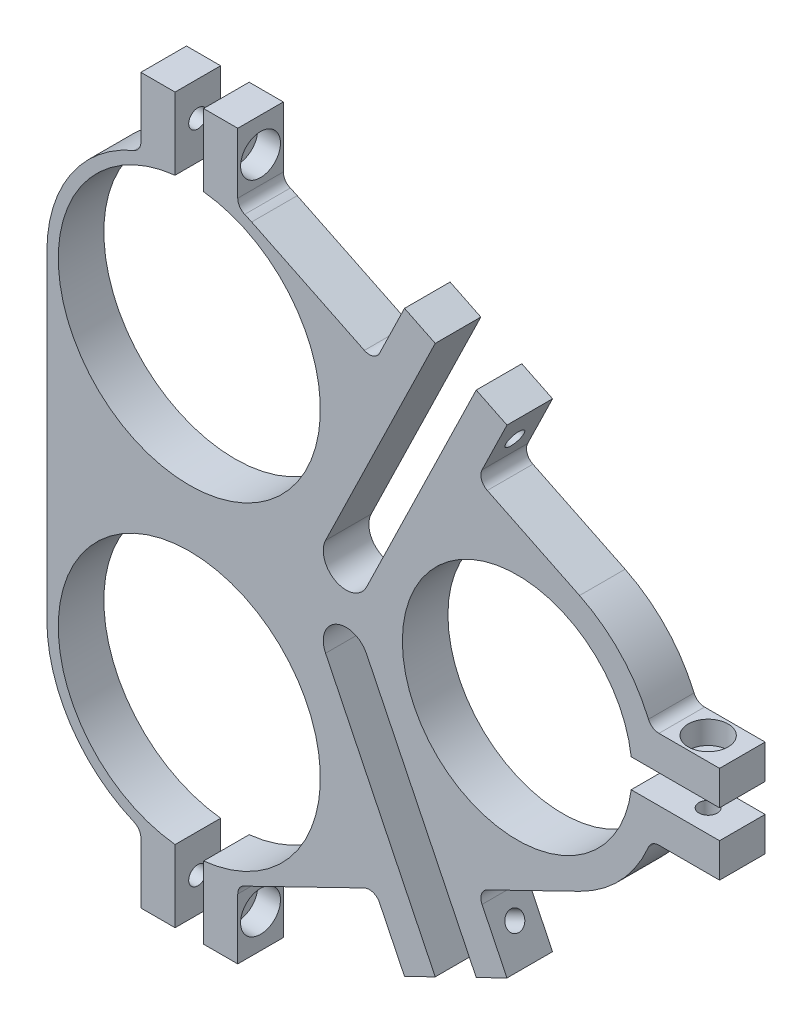
SolidWorks part; units mm, degrees
ref_plane "Front Plane" through (0, 0, 0) normal (0, 0, 1) x (1, 0, 0)
ref_plane "Top Plane" through (0, 0, 0) normal (0, 1, 0) x (1, 0, 0)
ref_plane "Right Plane" through (0, 0, 0) normal (1, 0, 0) x (0, 0, -1)
sketch "Sketch1" plane through (0, 0, 0) normal (0, 0, 1) x (1, 0, 0)
  line L0 (-39.6875, 88.9) -> (-39.6875, 0)
  line L1 (-39.6875, 44.45) -> (91.3606, 44.45) construction
  line L2 (17.3633, 124.5877) -> (51.6235, 107.919)
  line L3 (3.9688, -36.2962) -> (3.9688, -56.3731)
  line L4 (0, 88.9) -> (0, 0) construction
  line L5 (-13.4938, -37.3231) -> (-13.4938, -56.3731)
  line L6 (3.9688, -56.3731) -> (13.4938, -56.3731)
  line L7 (-3.9688, -56.3731) -> (-13.4938, -56.3731)
  line L8 (13.4938, -37.3231) -> (13.4938, -56.3731)
  line L9 (-3.9687, -36.2962) -> (-3.9688, -56.3731)
  line L10 (17.3633, -35.6877) -> (51.6235, -19.019)
  line L11 (13.4938, 126.2231) -> (13.4938, 145.2731)
  line L12 (-3.9688, 145.2731) -> (-13.4938, 145.2731)
  line L13 (3.9688, 145.2731) -> (13.4938, 145.2731)
  line L14 (3.9688, 145.2731) -> (3.9688, 125.1962)
  line L15 (-13.4938, 126.2231) -> (-13.4938, 145.2731)
  line L16 (60.1886, 103.7518) -> (71.6086, 98.1955) construction
  line L17 (60.1886, 103.7518) -> (37.9636, 58.0715)
  line L18 (-3.9688, 145.2731) -> (-3.9688, 125.1962)
  line L19 (71.6086, 98.1955) -> (49.3836, 52.5152)
  line L20 (37.9636, 58.0715) -> (49.3836, 52.5152) construction
  line L21 (60.1886, -14.8518) -> (37.9636, 30.8285)
  line L22 (60.1886, 103.7518) -> (68.5229, 120.8819)
  line L23 (3.9688, 145.2731) -> (-3.9688, 145.2731) construction
  line L24 (51.6235, 107.919) -> (59.9579, 125.0491)
  line L25 (3.9688, -56.3731) -> (-3.9688, -56.3731) construction
  line L26 (68.5229, 120.8819) -> (59.9579, 125.0491)
  line L27 (43.6736, 55.2934) -> (65.8986, 100.9737) construction
  line L28 (71.6086, 98.1955) -> (79.943, 115.3257)
  line L29 (79.943, 115.3257) -> (88.5081, 111.1585)
  line L30 (80.1737, 94.0284) -> (88.5081, 111.1585)
  line L31 (80.1737, 94.0284) -> (108.7239, 80.1377)
  line L32 (71.6086, -9.2955) -> (49.3836, 36.3848)
  line L33 (80.1737, -5.1284) -> (88.5081, -22.2585)
  line L34 (79.943, -26.4257) -> (88.5081, -22.2585)
  line L35 (71.6086, -9.2955) -> (79.943, -26.4257)
  line L36 (60.1886, -14.8518) -> (68.5229, -31.9819)
  line L37 (68.5229, -31.9819) -> (59.9579, -36.1491)
  line L38 (51.6235, -19.019) -> (59.9579, -36.1491)
  line L39 (43.6736, 33.6066) -> (65.8986, -12.0737) construction
  line L40 (60.1886, -14.8518) -> (71.6086, -9.2955) construction
  line L41 (80.1737, -5.1284) -> (108.7239, 8.7623)
  line L42 (123.1176, 48.4187) -> (147.7337, 48.4187)
  line L43 (147.7337, 48.4187) -> (147.7337, 57.9437)
  line L44 (147.7337, 57.9437) -> (128.6837, 57.9437)
  line L45 (123.1176, 40.4812) -> (147.7337, 40.4812)
  line L46 (147.7337, 40.4812) -> (147.7337, 30.9563)
  line L47 (147.7337, 30.9563) -> (128.6837, 30.9562)
  arc A0 (3.9688, -36.2962) -> (-3.9687, -36.2962) centre (0, 0) ccw
  arc A1 (-3.9688, 125.1962) -> (3.9688, 125.1962) centre (0, 88.9) ccw
  arc A2 (13.4938, 126.2231) -> (17.3633, 124.5877) centre (0, 88.9) cw
  arc A3 (-39.6875, 0) -> (-13.4938, -37.3231) centre (0, 0) ccw
  arc A4 (123.1176, 48.4187) -> (123.1176, 40.4812) centre (91.3606, 44.45) ccw
  arc A5 (13.4938, -37.3231) -> (17.3633, -35.6877) centre (0, 0) ccw
  arc A6 (-39.6875, 88.9) -> (-13.4938, 126.2231) centre (0, 88.9) cw
  arc A7 (128.6837, 57.9437) -> (128.6837, 30.9562) centre (91.3606, 44.45) ccw construction
  circle A8 centre (0, 0) radius 36.5125 construction
  circle A9 centre (0, 88.9) radius 36.5125 construction
  circle A10 centre (0, 0) radius 39.6875 construction
  circle A11 centre (91.3606, 44.45) radius 36.5125 construction
  circle A12 centre (0, 88.9) radius 39.6875 construction
  arc A13 (108.7239, 80.1377) -> (128.6837, 57.9437) centre (91.3606, 44.45) cw
  circle A14 centre (43.6736, 55.2934) radius 6.35 construction
  arc A15 (37.9636, 58.0715) -> (49.3836, 52.5152) centre (43.6736, 55.2934) ccw
  circle A16 centre (43.6736, 33.6066) radius 6.35 construction
  arc A17 (37.9636, 30.8285) -> (49.3836, 36.3848) centre (43.6736, 33.6066) cw
  arc A18 (128.6837, 30.9562) -> (108.7239, 8.7623) centre (91.3606, 44.45) cw
  point P14 (0, 36.5125)
  dimension "D2" = 64.008
  dimension "D4" = 73.025
  dimension "D5" = 73.025
  dimension "D7" = 79.375
  dimension "D9" = 79.375
  dimension "D10" = 73.025
  dimension "D11" = 12.7
  dimension "D1" = 7.9375
  dimension "D3" = 88.9
  dimension "D6" = 9.525
  dimension "D8" = 19.05
  dimension "D12" = 101.6
  dimension "D13" = 47.625
  dimension "D14" = 50.8
  dimension "D15" = 19.05
  dimension "D16" = 9.525
  dimension "D17" = 9.525
  dimension "D18" = 7.9375
  dimension "D19" = 19.05
extrude "Extrude1" add sketch "Sketch1" along normal mid plane 12.7
hole_wizard "CBORE for 1/4 Socket Head Cap Screw1" positions "Sketch3" profile "Sketch2" counterbore size "1/4" standard "Ansi Inch" end condition up to next
sketch "Sketch3" plane through (13.4938, 0, 0) normal (1, 0, 0) x (0, 0, -1)
  line L0 (6.35, 145.2731) -> (-6.35, 126.2231) construction
  point P0 (0, 135.7481)
sketch "Sketch2" plane through (13.4938, 135.7481, 0) normal (0, 1, 0) x (0, 0, -1)
  line L0 (0, 0) -> (0, 9.525)
  line L1 (0, 9.525) -> (3.3782, 9.525)
  line L3 (3.3782, 9.525) -> (3.3782, 6.35)
  line L4 (3.3782, 6.35) -> (5.5562, 6.35)
  line L5 (5.5562, 6.35) -> (5.5562, 0)
  line L7 (5.5562, 0) -> (0, 0)
  line L11 (0, -6.35) -> (0, 107.95) construction
  dimension "Thru Hole Dia." = 6.7564
  dimension "Thru Hole Depth" = 9.525
  dimension "C'Bore Dia." = 11.1125
  dimension "C'Bore Depth" = 6.35
hole_wizard "1/4-20 Tapped Hole1" positions "Sketch5" profile "Sketch4" tap size "1/4-20" standard "Ansi Inch" end condition through all
sketch "Sketch5" plane through (-3.9688, 0, 0) normal (1, 0, 0) x (0, 0, -1)
  point P0 (0, 135.7481)
sketch "Sketch4" plane through (-3.9688, 135.7481, 0) normal (0, 1, 0) x (0, 0, -1)
  line L0 (0, 0) -> (0, 35.7188)
  line L1 (0, 35.7188) -> (2.5527, 35.7188)
  line L2 (2.5527, 35.7188) -> (2.5527, 0)
  line L5 (2.5527, 0) -> (0, 0)
  line L11 (0, -6.35) -> (0, 107.95) construction
  dimension "Thru Tap Drill Dia." = 5.1054
  dimension "Thru Tap Drill Depth" = 35.7188
cosmetic thread "Hole Thread1" parameters "D2"=6.35
hole_wizard "CBORE for 1/4 Socket Head Cap Screw3" positions "Sketch16" profile "Sketch17" counterbore size "1/4" standard "Ansi Inch" end condition up to next
sketch "Sketch16" plane through (13.4938, 0, 0) normal (1, 0, 0) x (0, 0, -1)
  line L0 (6.35, -37.3231) -> (-6.35, -56.3731) construction
  point P0 (0, -46.8481)
sketch "Sketch17" plane through (13.4938, -46.8481, 0) normal (0, 1, 0) x (0, 0, -1)
  line L0 (0, 0) -> (0, 9.525)
  line L1 (0, 9.525) -> (3.3782, 9.525)
  line L3 (3.3782, 9.525) -> (3.3782, 6.35)
  line L4 (3.3782, 6.35) -> (5.5562, 6.35)
  line L5 (5.5562, 6.35) -> (5.5562, 0)
  line L7 (5.5562, 0) -> (0, 0)
  line L11 (0, -6.35) -> (0, 107.95) construction
  dimension "Thru Hole Dia." = 6.7564
  dimension "Thru Hole Depth" = 9.525
  dimension "C'Bore Dia." = 11.1125
  dimension "C'Bore Depth" = 6.35
hole_wizard "1/4-20 Tapped Hole4" positions "Sketch19" profile "Sketch21" tap size "1/4-20" standard "Ansi Inch" end condition through all
sketch "Sketch19" plane through (-3.9687, 0, 0) normal (1, 0, 0) x (0, 0, -1)
  point P0 (0, -46.8481)
sketch "Sketch21" plane through (-3.9687, -46.8481, 0) normal (0, 1, 0) x (0, 0, -1)
  line L0 (0, 0) -> (0, 35.7188)
  line L1 (0, 35.7188) -> (2.5527, 35.7188)
  line L2 (2.5527, 35.7188) -> (2.5527, 0)
  line L5 (2.5527, 0) -> (0, 0)
  line L11 (0, -6.35) -> (0, 107.95) construction
  dimension "Thru Tap Drill Dia." = 5.1054
  dimension "Thru Tap Drill Depth" = 35.7188
cosmetic thread "Hole Thread4" parameters "D2"=6.35
sketch "Sketch29" plane through (27.8364, -13.5434, 0) normal (0.8992, -0.4375, 0) x (0, 0, -1)
  line L0 (6.35, 138.678) -> (-6.35, 119.628) construction
hole_wizard "Tap Drill for 1/4-20 Tap1" positions "Sketch30" profile "Sketch31" hole size "1/4-20" standard "ANSI Inch" end condition up to next
sketch "Sketch30" plane through (27.8364, -13.5434, 0) normal (0.8992, -0.4375, 0) x (0, 0, -1)
  line L0 (6.35, 138.678) -> (-6.35, 119.628) construction
  point P0 (0, 129.153)
sketch "Sketch31" plane through (84.3409, 102.5934, 0) normal (0, 0, 1) x (0.4375, 0.8992, 0)
  line L0 (0, 0) -> (0, 9.525)
  line L1 (0, 9.525) -> (2.5527, 9.525)
  line L2 (2.5527, 9.525) -> (2.5527, 0)
  line L5 (2.5527, 0) -> (0, 0)
  line L11 (0, -6.35) -> (0, 107.95) construction
  dimension "Thru Hole Dia." = 5.1054
  dimension "Thru Hole Depth" = 9.525
sketch "Sketch41" plane through (0, 57.9437, 0) normal (0, 1, 0) x (1, 0, 0)
  line L0 (147.7337, 6.35) -> (128.6837, -6.35) construction
hole_wizard "CBORE for 1/4 Socket Head Cap Screw6" positions "Sketch42" profile "Sketch43" counterbore size "1/4" standard "ANSI Inch" end condition up to next
sketch "Sketch42" plane through (0, 57.9437, 0) normal (0, 1, 0) x (1, 0, 0)
  line L0 (147.7337, 6.35) -> (128.6837, -6.35) construction
  point P0 (138.2087, 0)
sketch "Sketch43" plane through (138.2087, 57.9437, 0) normal (1, 0, 0) x (0, 0, 1)
  line L0 (0, 0) -> (0, 9.525)
  line L1 (0, 9.525) -> (3.3782, 9.525)
  line L3 (3.3782, 9.525) -> (3.3782, 6.35)
  line L4 (3.3782, 6.35) -> (5.5562, 6.35)
  line L5 (5.5562, 6.35) -> (5.5563, 0)
  line L7 (5.5563, 0) -> (0, 0)
  line L11 (0, -6.35) -> (0, 107.95) construction
  dimension "Thru Hole Dia." = 6.7564
  dimension "Thru Hole Depth" = 9.525
  dimension "C'Bore Dia." = 11.1125
  dimension "C'Bore Depth" = 6.35
hole_wizard "1/4-20 Tapped Hole7" positions "Sketch44" profile "Sketch45" tap size "1/4-20" standard "ANSI Inch" end condition up to next
sketch "Sketch44" plane through (0, 40.4813, 0) normal (0, 1, 0) x (1, 0, 0)
  line L0 (147.7337, 6.35) -> (128.6837, -6.35) construction
  point P0 (138.2087, 0)
sketch "Sketch45" plane through (138.2087, 40.4813, 0) normal (1, 0, 0) x (0, 0, 1)
  line L0 (0, 0) -> (0, 9.525)
  line L1 (0, 9.525) -> (2.5527, 9.525)
  line L2 (2.5527, 9.525) -> (2.5527, 0)
  line L5 (2.5527, 0) -> (0, 0)
  line L11 (0, -6.35) -> (0, 107.95) construction
  dimension "Thru Tap Drill Dia." = 5.1054
  dimension "Thru Tap Drill Depth" = 9.525
cosmetic thread "Hole Thread7" parameters "D2"=6.35
sketch "Sketch46" plane through (62.8104, 30.5594, 0) normal (0.8992, 0.4375, 0) x (0, 0, -1)
  line L0 (-6.35, -39.6875) -> (6.35, -58.7375) construction
hole_wizard "Tap Drill for 1/4-20 Tap2" positions "Sketch47" profile "Sketch48" hole size "1/4-20" standard "ANSI Inch" end condition up to next
sketch "Sketch47" plane through (62.8104, 30.5594, 0) normal (0.8992, 0.4375, 0) x (0, 0, -1)
  line L0 (-6.35, -39.6875) -> (6.35, -58.7375) construction
  point P0 (0, -49.2125)
sketch "Sketch48" plane through (84.3409, -13.6934, 0) normal (0, 0, 1) x (-0.4375, 0.8992, 0)
  line L0 (0, 0) -> (0, 9.525)
  line L1 (0, 9.525) -> (2.5527, 9.525)
  line L2 (2.5527, 9.525) -> (2.5527, 0)
  line L5 (2.5527, 0) -> (0, 0)
  line L11 (0, -6.35) -> (0, 107.95) construction
  dimension "Thru Hole Dia." = 5.1054
  dimension "Thru Hole Depth" = 9.525
fillet "Fillet1" radius 3.175 10 edges at (13.4938, 126.2231, 0) (-13.4938, 126.2231, 0) (-13.4938, -37.3231, 0) (13.4938, -37.3231, 0) (51.6235, 107.919, 0) (80.1737, 94.0284, 0) (128.6837, 30.9562, 0) (128.6837, 57.9437, 0) (51.6235, -19.019, 0) (80.1737, -5.1284, 0)
